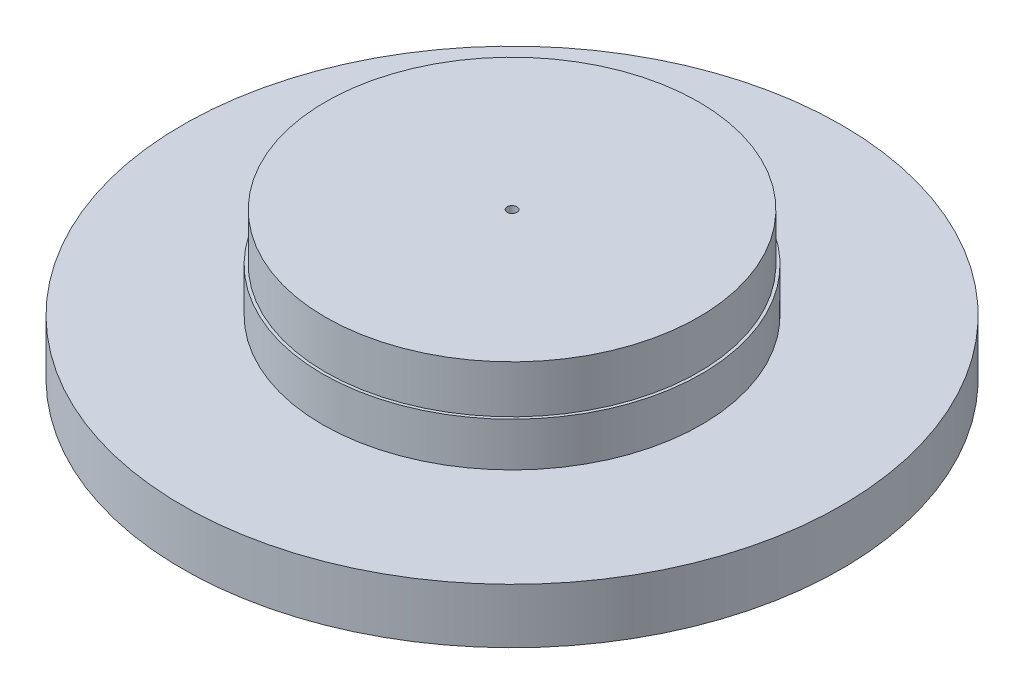
SolidWorks part; units mm, degrees
ref_plane "Front Plane" through (0, 0, 0) normal (0, 0, 1) x (1, 0, 0)
ref_plane "Top Plane" through (0, 0, 0) normal (0, 1, 0) x (1, 0, 0)
ref_plane "Right Plane" through (0, 0, 0) normal (1, 0, 0) x (0, 0, -1)
sketch "Sketch1" plane through (0, 0, 0) normal (0, 1, 0) x (1, 0, 0)
  circle A0 centre (0, 0) radius 129.413
  circle A1 centre (0, 0) radius 131.445
  circle A2 centre (0, 0) radius 228.6
extrude "Boss-Extrude1" add sketch "Sketch1" along normal blind 38.1 contours A2 A1 region at (-222.1342, 0, 0)
extrude "Boss-Extrude2" add sketch "Sketch1<3>" along normal blind 68.58 contours A1 A0 region at (-131.0732, 0, 0)
sketch "Sketch1<3>" plane through (0, 0, 0) normal (0, 1, 0) x (1, 0, 0) same geometry as "Sketch1"
extrude "Boss-Extrude3" add sketch "Sketch1<4>" along normal blind 101.6 contours A0 region at (0, 0, 0)
sketch "Sketch1<4>" plane through (0, 0, 0) normal (0, 1, 0) x (1, 0, 0) same geometry as "Sketch1"
hole_wizard "CSK for 1/4 Flat Head Machine Screw (100)1" positions "Sketch2" profile "Sketch3" countersink size "1/4" standard "ANSI Inch" end condition through all
sketch "Sketch2" plane through (0, 0, 0) normal (0, -1, 0) x (-1, 0, 0)
  point P0 (0, 0)
sketch "Sketch3" plane through (0, 0, 0) normal (1, 0, 0) x (0, 0, -1)
  line L0 (0, 0) -> (0, 101.6)
  line L1 (0, 101.6) -> (3.3782, 101.6)
  line L2 (3.3782, 101.6) -> (3.3782, 2.5682)
  line L3 (3.3782, 2.5682) -> (6.4389, 0)
  line L5 (6.4389, 0) -> (0, 0)
  line L6 (-3.3782, 2.5682) -> (-6.4389, 0) construction
  line L11 (0, -6.35) -> (0, 107.95) construction
  dimension "Thru Hole Dia." = 6.7564
  dimension "Thru Hole Depth" = 101.6
  dimension "Near C'Sink Dia." = 12.8778
  dimension "Near C'Sink Angle" = 100
